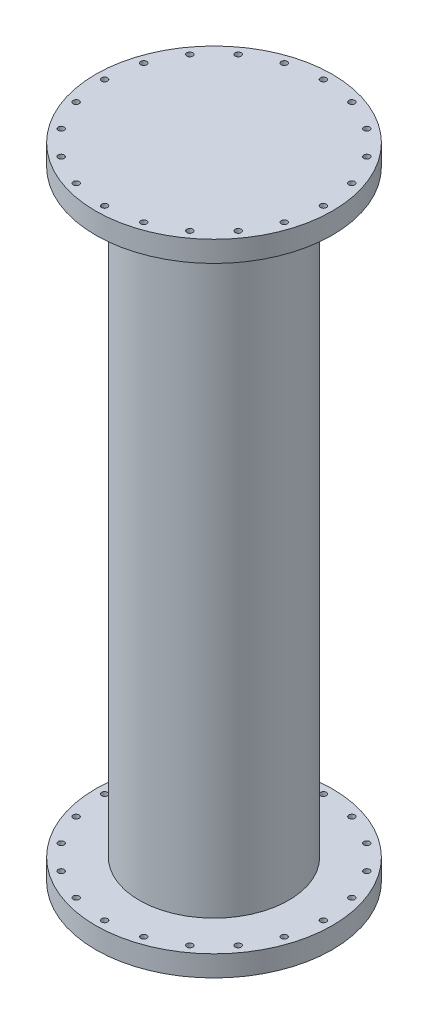
SolidWorks part; units mm, degrees
ref_plane "Plan de face" through (0, 0, 0) normal (0, 0, 1) x (1, 0, 0)
ref_plane "Plan de dessus" through (0, 0, 0) normal (0, 1, 0) x (1, 0, 0)
ref_plane "Plan de droite" through (0, 0, 0) normal (1, 0, 0) x (0, 0, -1)
sketch "Esquisse1" plane through (0, 0, 0) normal (0, 0, 1) x (1, 0, 0)
  line L0 (0, 0) -> (0, -1756.5308) construction
  line L1 (0, 0) -> (396, 0)
  line L2 (0, 0) -> (0, -70)
  line L3 (0, -70) -> (200, -70)
  line L4 (396, 0) -> (396, -70)
  line L26 (250, -70) -> (396, -70)
  line L27 (250, -2070) -> (396, -2070)
  line L29 (200, -70) -> (200, -2070)
  line L31 (250, -70) -> (250, -2070)
  line L32 (0, -2070) -> (200, -2070)
  line L33 (0, -2070) -> (0, -2140)
  line L34 (0, -2140) -> (396, -2140)
  line L35 (396, -2070) -> (396, -2140)
  dimension "D1" = 396
  dimension "D2" = 70
  dimension "D3" = 70
  dimension "D4" = 396
  dimension "D5" = 250
  dimension "D6" = 200
  dimension "D7" = 2000
revolve "Révolution1" add sketch "Esquisse1" angle 360 about L0
sketch "Esquisse2" plane through (0, 0, 0) normal (0, 1, 0) x (1, 0, 0)
  circle A0 centre (366, 0) radius 10
  dimension "D2" = 20
  dimension "D1" = 366
extrude "Enlèv. mat.-Extru.1" cut sketch "Esquisse2" against normal through all
pattern_circular "Répétition circulaire1" count 20 over 360 about axis through (0, 0, 0) along (0, 1, 0) of "Enlèv. mat.-Extru.1"
sketch "Esquisse3" plane through (0, -2140, 0) normal (0, 1, 0) x (1, 0, 0)
  circle A0 centre (0, 0) radius 255.3935
sketch "Esquisse4" plane through (0, -2140, 0) normal (0, -1, 0) x (1, 0, 0)
  circle A0 centre (0, 0) radius 255.3935
  circle A1 centre (0, 0) radius 200
  circle A2 centre (0, 230.8199) radius 10
